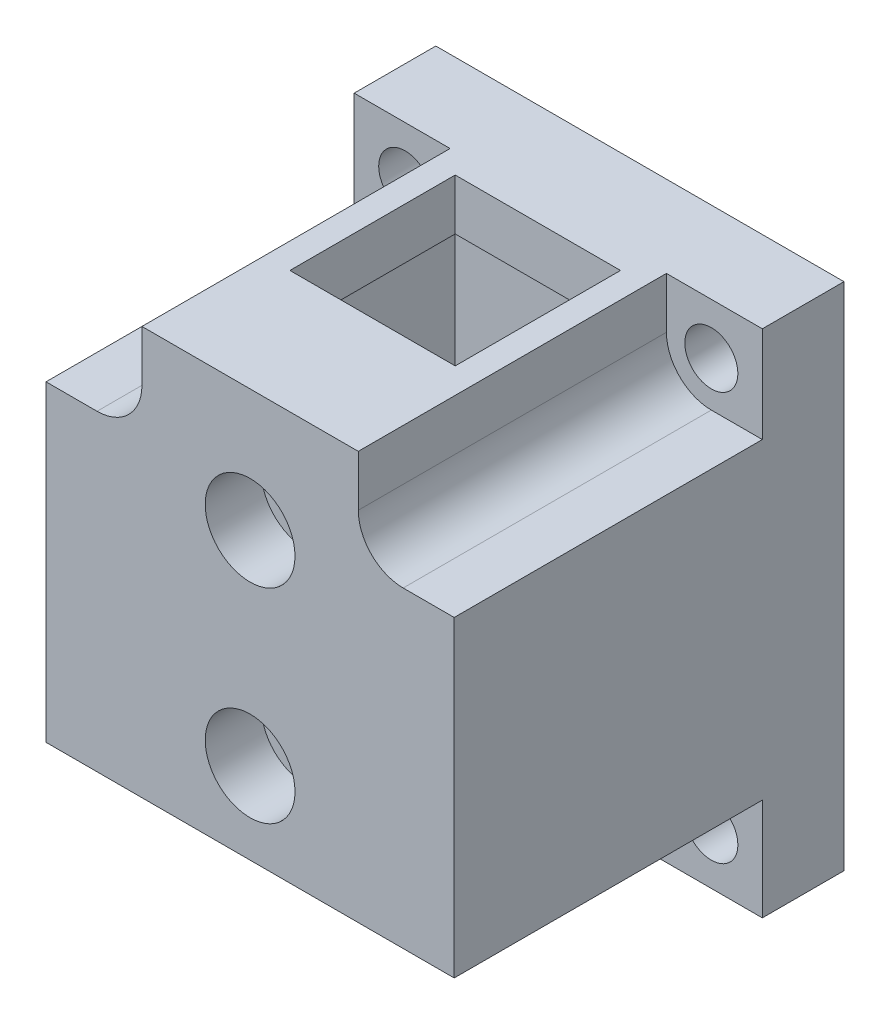
SolidWorks part; units mm, degrees
ref_plane "Front Plane" through (0, 0, 0) normal (0, 0, 1) x (1, 0, 0)
ref_plane "Top Plane" through (0, 0, 0) normal (0, 1, 0) x (1, 0, 0)
ref_plane "Right Plane" through (0, 0, 0) normal (1, 0, 0) x (0, 0, -1)
sketch "Sketch1" plane through (0, 0, 0) normal (0, 0, 1) x (1, 0, 0)
  line L1 (0, 0) -> (40, 0)
  line L2 (0, 0) -> (0, 40)
  line L3 (0, 40) -> (40, 40)
  line L4 (40, 0) -> (40, 40)
  line L5 (10, 0) -> (30, 0) construction
  line L6 (10, 0) -> (10, 31.486) construction
  line L7 (10, 31.486) -> (30, 31.486) construction
  line L8 (30, 0) -> (30, 31.486) construction
  dimension "D1" = 40
  dimension "D2" = 40
  dimension "D3" = 20
  dimension "D4" = 10
extrude "Boss-Extrude1" add sketch "Sketch1" along normal blind 8
sketch "Sketch6" plane through (0, 0, 0) normal (0, -1, 0) x (1, 0, 0)
  line L0 (40, 8) -> (40, 0) construction
  line L1 (0, 0) -> (40, 0)
  line L2 (0, 0) -> (0, 8)
  line L3 (0, 8) -> (40, 8)
  line L4 (40, 0) -> (40, 8)
  dimension "D1" = 8
extrude "Boss-Extrude4" add sketch "Sketch6" along normal blind 10
sketch "Sketch2" plane through (0, 0, 8) normal (0, 0, 1) x (1, 0, 0)
  line L1 (0, 40) -> (10, 40)
  line L2 (0, 40) -> (0, 0)
  line L3 (0, 0) -> (9.9, 0)
  line L4 (9.9, 35) -> (9.9, 0)
  line L5 (40, -10) -> (0, -10) construction
  line L6 (40, 40) -> (30, 40)
  line L7 (40, 40) -> (40, 0)
  line L8 (40, 0) -> (30.1, 0)
  line L9 (30.1, 35) -> (30.1, 0)
  line L10 (10, 40) -> (30, 40)
  line L12 (9.9, 35) -> (30.1, 35)
  point P14 (0, 0)
  point P15 (0, 0)
  dimension "D1" = 9.9
  dimension "D2" = 9.9
  dimension "D3" = 5
  dimension "D4" = 10
extrude "Boss-Extrude2" add sketch "Sketch2" along normal blind 20.2
sketch "Sketch3" plane through (0, 0, 28.2) normal (0, 0, 1) x (1, 0, 0)
  line L5 (0, 40) -> (40, 40)
  line L6 (0, 40) -> (0, 0)
  line L7 (0, 0) -> (40, 0)
  line L8 (40, 40) -> (40, 0)
extrude "Boss-Extrude3" add sketch "Sketch3" along normal blind 10
sketch "Sketch4" plane through (0, 0, 38.2) normal (0, 0, 1) x (1, 0, 0)
  line L0 (20, -10) -> (20, 42.5917) construction
  line L5 (40, -10) -> (0, -10) construction
  line L6 (0, 0) -> (40, 0) construction
  line L7 (40, 40) -> (0, 40) construction
  line L8 (0, 40) -> (0, 0) construction
  line L9 (40, 0) -> (40, 40) construction
  circle A0 centre (35, 35) radius 2.6
  circle A1 centre (35, -5) radius 2.6
  circle A2 centre (5, 35) radius 2.6
  circle A3 centre (5, -5) radius 2.6
  circle A4 centre (20, 28) radius 2.6
  circle A5 centre (20, 8) radius 2.6
  point P16 (20, 42.5917)
  point P17 (20, 40)
  point P18 (0, 0)
  point P19 (0, 0)
  point P24 (0, 0)
  point P25 (0, 0)
  point P26 (0, 0)
  point P27 (0, 0)
  point P28 (0, 0)
  point P29 (20, -10)
  point P32 (0, 0)
  point P33 (0, 0)
  point P34 (35, -9.5241)
  point P35 (5, -9.1486)
  point P39 (0, 0)
  dimension "D1" = 5.2
  dimension "D2" = 12
  dimension "D3" = 5
  dimension "D4" = 5
  dimension "D5" = 8
  dimension "D6" = 5
  dimension "D7" = 5
extrude "Cut-Extrude1" cut sketch "Sketch4" against normal through all
sketch "Sketch5" plane through (0, 0, 38.2) normal (0, 0, 1) x (1, 0, 0)
  line L0 (9.4, 35) -> (9.4, 40)
  line L2 (9.4, 40) -> (0, 40)
  line L3 (5, 30.6) -> (0, 30.6)
  line L5 (0, 30.6) -> (0, 40)
  line L6 (30.6, 35) -> (30.6, 40)
  line L7 (30.6, 40) -> (40, 40)
  line L8 (40, 40) -> (40, 30.6)
  line L10 (40, 30.6) -> (35, 30.6)
  line L12 (0, 40) -> (0, 0) construction
  line L15 (40, 40) -> (0, 40) construction
  line L16 (40, 0) -> (40, 40) construction
  circle A0 centre (5, -5) radius 2.6 construction
  circle A1 centre (20, 8) radius 2.6 construction
  circle A2 centre (35, -5) radius 2.6 construction
  circle A3 centre (35, 35) radius 2.6 construction
  circle A4 centre (20, 28) radius 2.6 construction
  circle A5 centre (5, 35) radius 2.6 construction
  circle A6 centre (5, -5) radius 2.6 construction
  circle A7 centre (20, 8) radius 2.6 construction
  circle A8 centre (35, -5) radius 2.6 construction
  circle A9 centre (35, 35) radius 2.6 construction
  circle A10 centre (20, 28) radius 2.6 construction
  circle A11 centre (5, 35) radius 2.6 construction
  circle A12 centre (5, 35) radius 4.4
  circle A13 centre (20, 28) radius 4.4
  circle A14 centre (35, 35) radius 4.4
  circle A15 centre (35, -5) radius 4.4
  circle A16 centre (20, 8) radius 4.4
  circle A17 centre (5, -5) radius 4.4
  point P32 (0, 0)
  point P36 (0, 0)
  point P43 (0, 0)
  point P45 (0, 0)
  point P47 (0, 0)
  circle M5 centre (20, 28) radius 2.6
  circle M7 centre (5, 35) radius 2.6
  circle M9 centre (20, 8) radius 2.6
  circle M10 centre (35, 35) radius 2.6
  dimension "D1" = 8.8
extrude "Cut-Extrude2" cut sketch "Sketch5" against normal offset from surface (30.2 mm away) 8 contours A12 M7 | A14 M10 | A15 | A17 | A12 L0 L3 | A14 L10 L6 | A15 | A17 region at (1.7947, 38.2053, 38.2) region at (8.0233, 31.9767, 38.2) region at (30.7329, 37.5, 38.2) region at (35, 39.2755, 38.2) region at (35, -5, 38.2) region at (5, -5, 38.2) up to face at (22.6, 28, 0)
extrude "Cut-Extrude3" cut sketch "Sketch5<3>" against normal blind 5.5 contours A13 M5 | A16 M9 region at (15.7245, 28, 38.2) region at (15.7245, 8, 38.2)
sketch "Sketch5<3>" plane through (0, 0, 38.2) normal (0, 0, 1) x (1, 0, 0) same geometry as "Sketch5"
extrude "Cut-Extrude4" cut sketch "Sketch5<4>" along normal blind 5.5 from surface contours A13 M5 | A16 M9 region at (15.7245, 28, 38.2) region at (15.7245, 8, 38.2) starting at face at (22.6, 28, 0)
sketch "Sketch5<4>" plane through (0, 0, 38.2) normal (0, 0, 1) x (1, 0, 0) same geometry as "Sketch5"
sketch "Sketch7" plane through (0, 35, 0) normal (0, -1, 0) x (1, 0, 0)
  line L12 (11.9, 10) -> (28.1, 10)
  line L13 (28.1, 10) -> (28.1, 26.2)
  line L14 (28.1, 26.2) -> (11.9, 26.2)
  line L15 (11.9, 26.2) -> (11.9, 10)
  line L16 (11.9, 10) -> (28.1, 10)
  line L17 (28.1, 10) -> (28.1, 26.2)
  line L18 (28.1, 26.2) -> (11.9, 26.2)
  line L19 (11.9, 26.2) -> (11.9, 10)
  dimension "D1" = 2
extrude "Cut-Extrude5" cut sketch "Sketch7" against normal blind 10
chamfer "Chamfer1" distance 0.5 angle 45 3 edges at (30.1, 0, 18.1) (20, 0, 28.2) (9.9, 0, 18.1)
